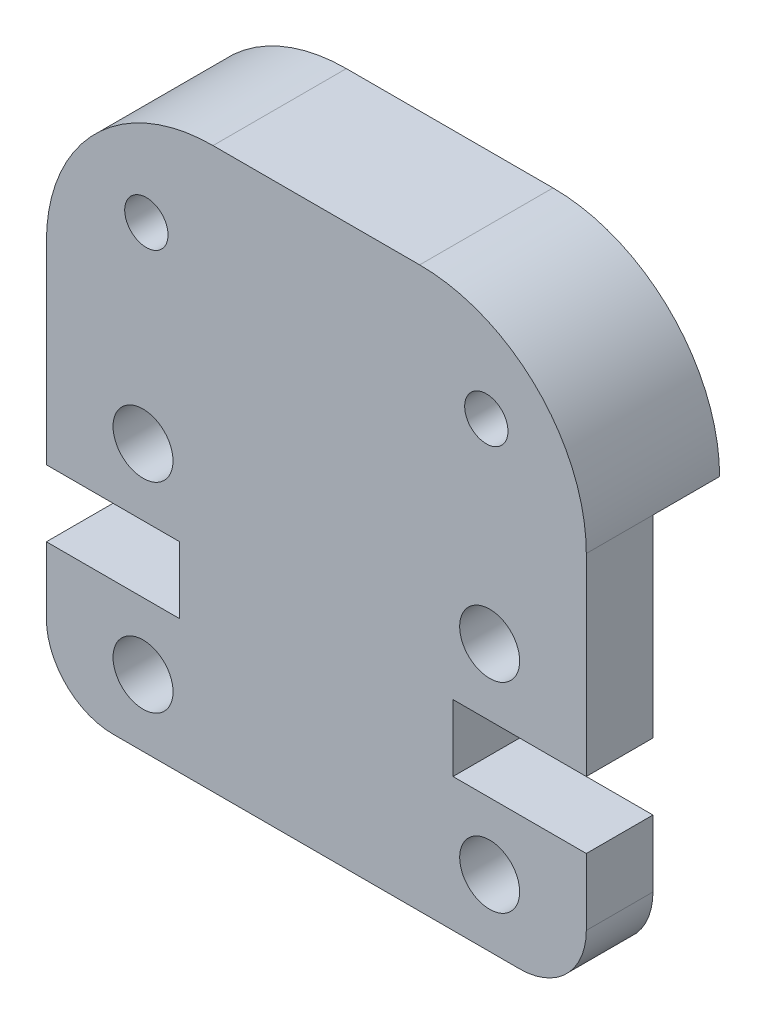
SolidWorks part; units mm, degrees
ref_plane "Front Plane" through (0, 0, 0) normal (0, 0, 1) x (1, 0, 0)
ref_plane "Top Plane" through (0, 0, 0) normal (0, 1, 0) x (1, 0, 0)
ref_plane "Right Plane" through (0, 0, 0) normal (1, 0, 0) x (0, 0, -1)
sketch "Sketch1" plane through (0, 0, 0) normal (0, 0, 1) x (1, 0, 0)
  line L0 (0, 6) -> (0, 11.795)
  line L1 (12.2, 4) -> (16.2, 4)
  line L2 (5, 16.795) -> (11.2, 16.795)
  line L3 (2, 0) -> (14.2, 0)
  line L4 (12.2, 6) -> (12.2, 4)
  line L5 (0, 2) -> (0, 4)
  line L6 (0, 6) -> (4, 6)
  line L7 (16.2, 6) -> (12.2, 6)
  line L8 (4, 6) -> (4, 4)
  line L9 (4, 4) -> (0, 4)
  line L10 (16.2, 2) -> (16.2, 4)
  line L11 (16.2, 6) -> (16.2, 11.795)
  line L12 (8.1, 16.795) -> (8.1, 0) construction
  circle A0 centre (13.3, 2) radius 0.9
  arc A1 (5, 16.795) -> (0, 11.795) centre (5, 11.795) ccw
  circle A2 centre (13.3, 8) radius 0.9
  circle A3 centre (3, 13.795) radius 0.65
  arc A4 (16.2, 2) -> (14.2, 0) centre (14.2, 2) cw
  arc A5 (0, 2) -> (2, 0) centre (2, 2) ccw
  circle A6 centre (13.2, 13.795) radius 0.65
  circle A7 centre (2.9, 8) radius 0.9
  arc A8 (11.2, 16.795) -> (16.2, 11.795) centre (11.2, 11.795) cw
  circle A9 centre (2.9, 2) radius 0.9
  dimension "D1" = 1.8
  dimension "D2" = 1.3
  dimension "D3" = 5
  dimension "D4" = 2
  dimension "D5" = 3
  dimension "D6" = 8.1
  dimension "D7" = 8
  dimension "D9" = 16.795
  dimension "D8" = 3
extrude "Boss-Extrude1" add sketch "Sketch1" along normal blind 4
sketch "Sketch2" plane through (0, 0, 0) normal (0, 0, 1) x (1, 0, 0)
  line L0 (0, 0) -> (0, 11.795)
  line L1 (0, 11.795) -> (16.2, 11.795)
  line L2 (16.2, 11.795) -> (16.2, 0)
  line L3 (16.2, 0) -> (0, 0)
extrude "Cut-Extrude1" cut sketch "Sketch2" along normal blind 2
equation "\"D6@Sketch1\"= \"fingerWidth@parametersSketch@prostheticParameters.SLDPRT\" / 2 'DIP width"
equation "\"D9@Sketch1\"= \"HL@parametersSketch@prostheticParameters.SLDPRT\" * 0.107 - 3 'DIP length - Sil. Sht DIP"
equation "\"D1@Sketch1\"= 1.5 + \"tol1@parametersSketch@prostheticParameters.SLDPRT\""
equation "\"D2@Sketch1\"= 1 + \"tol1@parametersSketch@prostheticParameters.SLDPRT\""
